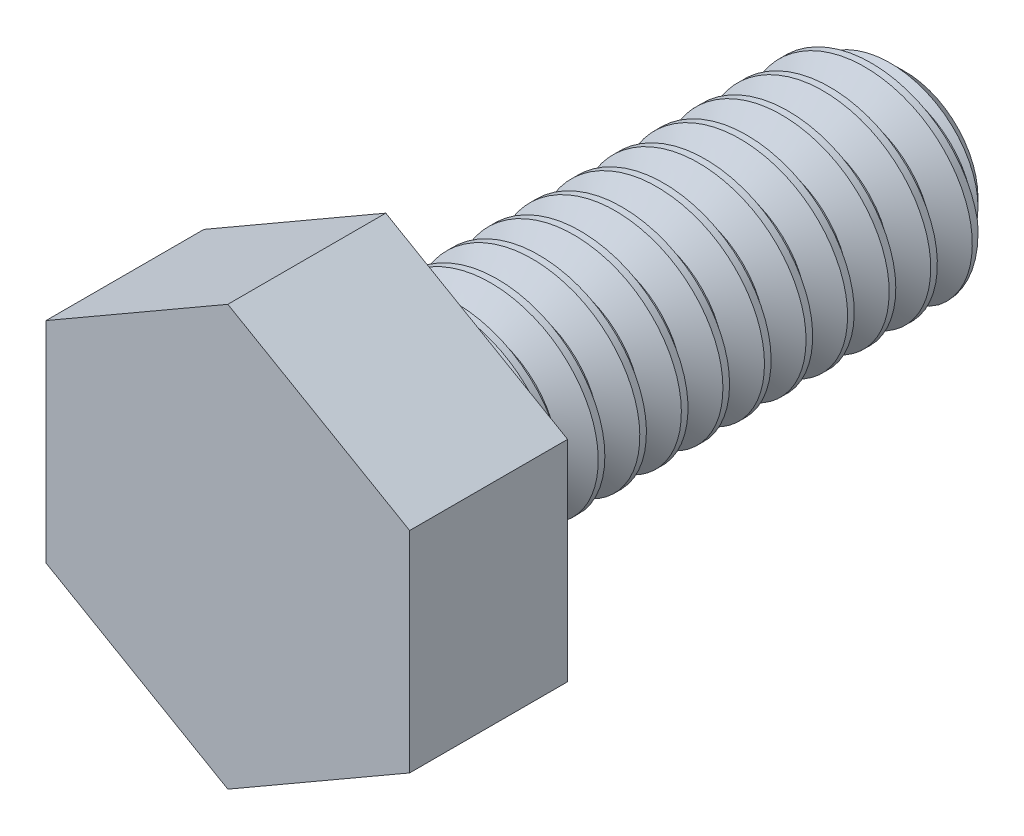
SolidWorks part; units mm, degrees
ref_plane "Front" through (0, 0, 0) normal (0, 0, 1) x (1, 0, 0)
ref_plane "Top" through (0, 0, 0) normal (0, 1, 0) x (1, 0, 0)
ref_plane "Right" through (0, 0, 0) normal (1, 0, 0) x (0, 0, -1)
sketch "Sketch1" plane through (0, 0, 0) normal (0, 0, 1) x (1, 0, 0)
  line L1 (-5.5562, -3.2079) -> (0, -6.4158)
  line L2 (0, -6.4158) -> (5.5563, -3.2079)
  line L3 (5.5563, -3.2079) -> (5.5562, 3.2079)
  line L4 (5.5562, 3.2079) -> (0, 6.4158)
  line L5 (0, 6.4158) -> (-5.5562, 3.2079)
  line L6 (-5.5562, 3.2079) -> (-5.5562, -3.2079)
  circle A0 centre (0, 0) radius 5.5562 construction
  circle A1 centre (0, 0) radius 5.5563 construction
  dimension "Head Dia" = 11.1125
extrude "Extrude3" add sketch "Sketch1" along normal blind 4.826
sketch "Sketch4" plane through (0, 0, 0) normal (1, 0, 0) x (0, 0, -1)
  line L0 (0, 0) -> (15.875, 0)
  line L3 (15.875, 0) -> (15.875, 3.175)
  line L4 (15.875, 3.175) -> (0, 3.175)
  line L6 (0, 3.175) -> (0, 0)
  line L9 (15.875, 3.175) -> (15.875, -3.175) construction
  dimension "dia" = 6.35
  dimension "length" = 15.875
revolve "Revolve1" add sketch "Sketch4" angle 360 about L0
sketch "Sketch13" plane through (0, 0, -15.875) normal (0, 0, -1) x (-1, 0, 0)
  circle A2 centre (0, 0) radius 3.175
curve "Helix/Spiral1" pitch 1.27 height 20.701 radius 3.175 centre (0, 0, -15.875) axis (0, 0, 1) start towards (1, 0, 0)
chamfer "Chamfer2" distance 0.9525 angle 45 1 edges at (3.175, 0, -15.875)
sketch "Sketch14" plane through (0, 0, 0) normal (1, 0, 0) x (0, 0, -1)
  line L0 (15.875, 3.2147) -> (16.9863, 3.2147)
  line L1 (16.9863, 3.2147) -> (16.51, 2.3555)
  line L2 (16.51, 2.3555) -> (16.3513, 2.3555)
  line L3 (16.3513, 2.3555) -> (15.875, 3.2147)
  line L4 (16.1131, 2.7851) -> (16.7481, 2.7851) construction
  dimension "D1" = 0.1588
  dimension "D2" = 58
  dimension "D3" = 0.635
  dimension "D4" = 0.0397
sweep "Cut-Sweep1" cut profiles "Sketch14" path "Helix/Spiral1"
ref_plane "Plane1" through (0, 0, 22.225) normal (0, 0, -1) x (-1, 0, 0)
sketch "Sketch29" [suppressed] plane through (0, 0, 28.575) normal (0, 0, -1) x (-1, 0, 0)
  circle A0 centre (0, 0) radius 1.7526 construction
  circle A1 centre (0, 0) radius 1.7526
  point P3 (0, -1.7526)
  point P4 (0, 1.7526)
equation "\"D3@Helix/Spiral1\" = \"Length@Sketch4\" + \"Head Ht@Extrude3\""
equation "\"D1@Sketch14\" = \"D4@Helix/Spiral1\" * .125"
equation "\"D3@Sketch14\" = \"D4@Helix/Spiral1\" * .5"
equation "\"D4@Sketch14\" = \"D1@Sketch14\" * .25"
equation "\"D1@Chamfer2\" = \"D4@Helix/Spiral1\" * .75"
